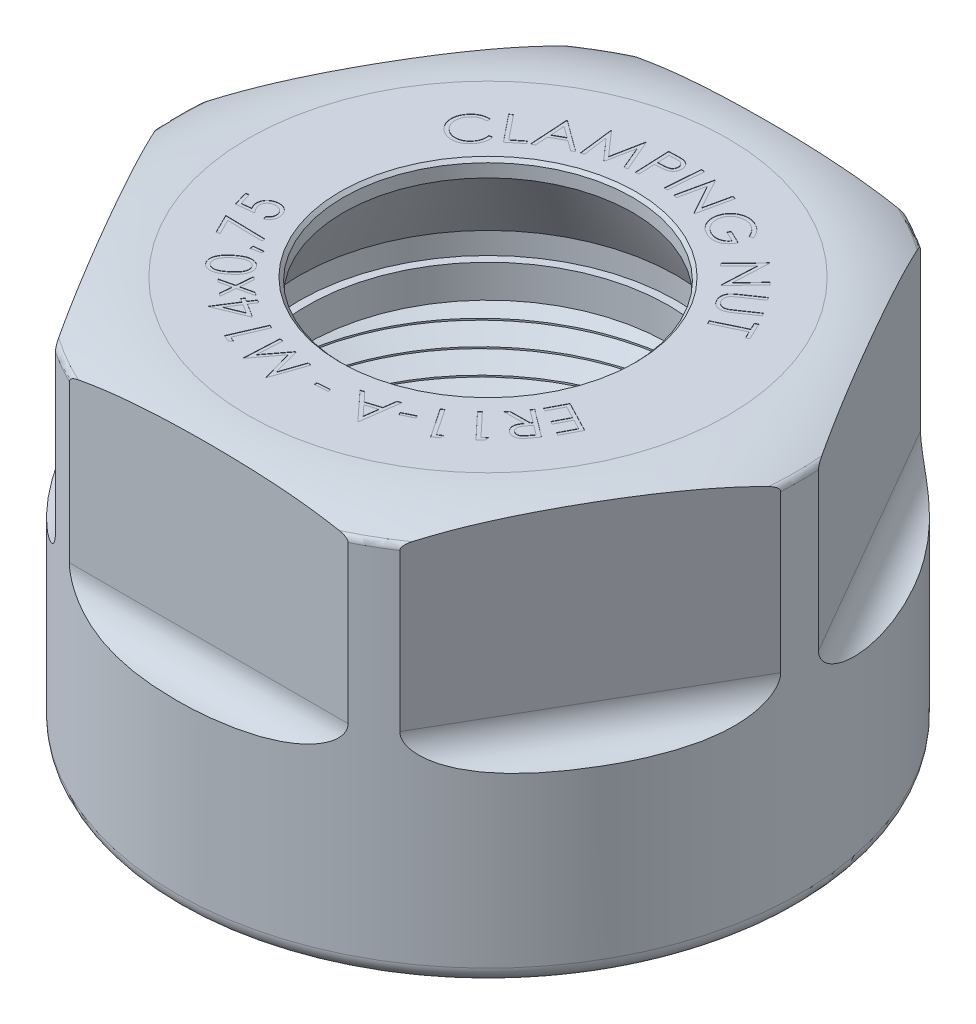
SolidWorks part; units mm, degrees
ref_plane "Front Plane" through (0, 0, 0) normal (0, 0, 1) x (1, 0, 0)
ref_plane "Top Plane" through (0, 0, 0) normal (0, 1, 0) x (1, 0, 0)
ref_plane "Right Plane" through (0, 0, 0) normal (1, 0, 0) x (0, 0, -1)
sketch "Sketch1" plane through (0, 0, 0) normal (0, 1, 0) x (1, 0, 0)
  circle A0 centre (0, 0) radius 9.5
  dimension "D1" = 19
extrude "Boss-Extrude1" add sketch "Sketch1" along normal blind 12
sketch "Sketch2" plane through (0, 12, 0) normal (0, 1, 0) x (1, 0, 0)
  line L1 (9.4825, 0.5758) -> (5.2399, 7.9242)
  line L2 (4.2426, 8.5) -> (-4.2426, 8.5)
  line L3 (-5.2399, 7.9242) -> (-9.4825, 0.5758)
  line L4 (-9.4825, -0.5758) -> (-5.2399, -7.9242)
  line L5 (-4.2426, -8.5) -> (4.2426, -8.5)
  line L6 (5.2399, -7.9242) -> (9.4825, -0.5758)
  circle A0 centre (0, 0) radius 8.5 construction
  circle A1 centre (0, 0) radius 9.5 construction
  arc A2 (-5.2399, 7.9242) -> (-9.4825, 0.5758) centre (0, 0) ccw
  arc A3 (4.2426, 8.5) -> (-4.2426, 8.5) centre (0, 0) ccw
  arc A4 (9.4825, 0.5758) -> (5.2399, 7.9242) centre (0, 0) ccw
  arc A5 (5.2399, -7.9242) -> (9.4825, -0.5758) centre (0, 0) ccw
  arc A6 (-4.2426, -8.5) -> (4.2426, -8.5) centre (0, 0) ccw
  arc A7 (-9.4825, -0.5758) -> (-5.2399, -7.9242) centre (0, 0) ccw
  dimension "D1" = 17
extrude "Cut-Extrude1" cut sketch "Sketch2" against normal blind 6.4
fillet "Fillet1" radius 1 6 edges at (-7.3612, 5.6, 4.25) (-7.3612, 5.6, -4.25) (0, 5.6, -8.5) (7.3612, 5.6, -4.25) (7.3612, 5.6, 4.25) (0, 5.6, 8.5)
sketch "Sketch3" plane through (0, 12, 0) normal (0, 1, 0) x (1, 0, 0)
  circle A0 centre (0, 0) radius 4.4
  dimension "D1" = 8.8
extrude "Cut-Extrude2" cut sketch "Sketch3" against normal up to next
sketch "Sketch5" plane through (0, 0, 0) normal (0, 0, 1) x (1, 0, 0)
  line L0 (-6.4, 0.3464) -> (-6.4, 6.7072)
  line L1 (-9.5, 0) -> (9.5, 0) construction
  line L2 (-6.4, 7.5) -> (-5.5, 7.5)
  line L3 (-5.5, 7.5) -> (-5.5, 8.5)
  line L4 (-5.5, 8.5) -> (-5.75, 8.5)
  line L7 (0, 11.5) -> (0, 0)
  line L8 (0, 0) -> (-6.4, 0)
  line L9 (4.4, 12) -> (-4.4, 12) construction
  line L10 (4.4, 12) -> (-4.4, 12) construction
  line L11 (-4.4, 12) -> (-4.4, 11.5) construction
  line L13 (-4.4, 11.5) -> (-4.4, 10.8242) construction
  line L14 (-4.4, 11.5) -> (0, 11.5)
  line L15 (-5.75, 8.5) -> (-5.75, 9.1617)
  line L16 (-5.75, 9.1617) -> (-4.4, 11.5)
  line L17 (-6.4, 7.5) -> (-7, 7.1536)
  line L18 (-7, 7.1536) -> (-7, 7.0536)
  line L19 (-7, 7.0536) -> (-6.4, 6.7072)
  line L20 (-6.4, 0.3464) -> (-7, 0)
  line L21 (-7, 0) -> (-6.4, 0)
  dimension "D1" = 6.4
  dimension "D2" = 5.5
  dimension "D3" = 1
  dimension "D4" = 30
  dimension "D5" = 0.5
  dimension "D6" = 7.5
  dimension "D7" = 5.75
  dimension "D8" = 60
  dimension "D9" = 7
  dimension "D10" = 0.1
revolve "Cut-Revolve1" cut sketch "Sketch5" angle 360 about L7
sketch "Sketch6" plane through (0, 0, 0) normal (0, 0, 1) x (1, 0, 0)
  line L0 (-9.5, 12) -> (-7.3, 12)
  line L1 (-5.2399, 12) -> (-9.4825, 12) construction
  line L3 (-9.5, 11.5) -> (-9.5, 12)
  line L4 (0, 0) -> (0, 12) construction
  line L5 (4.2426, 12) -> (-4.2426, 12) construction
  arc A0 (-7.3, 12) -> (-9.5, 11.5) centre (-7.3, 6.91) ccw
  dimension "D1" = 2.2
  dimension "D2" = 0.5
revolve "Cut-Revolve2" cut sketch "Sketch6" angle 360 about L4
fillet "Fillet2" radius 0.2 6 edges at (-9.5, 11.5, 0) (-4.75, 11.5, -8.2272) (4.75, 11.5, -8.2272) (9.5, 11.5, 0) (4.75, 11.5, 8.2272) (-4.75, 11.5, 8.2272)
fillet "Fillet3" radius 0.5 1 edges at (0, 0, 9.5)
sketch "Sketch7" plane through (0, 12, 0) normal (0, 1, 0) x (1, 0, 0)
  circle A0 centre (0, 0) radius 5.0417 construction
  text T0 "ER11-A - M14x0,75          CLAMPING NUT" font "Century Gothic" height in points 4
extrude "Cut-Extrude3" cut sketch "Sketch7" against normal blind 0.01
chamfer "Chamfer2" distance 0.1 angle 45 1 edges at (0, 12, 4.4)
sketch "Эскиз1" plane through (0, 0, 0) normal (0, -1, 0) x (1, 0, 0)
  circle A0 centre (0, 0) radius 7
  dimension "D1" = 14
curve "Спираль1" pitch 0.75 height 7.5 turns 10
ref_plane "Плоскость1" through (4.9497, 0, 4.9497) normal (0.707, 0.017, -0.707) x (-0.7068, -0.017, -0.7072)
sketch "Эскиз2" plane through (4.9497, 0, 4.9497) normal (0.707, 0.017, -0.707) x (-0.7068, -0.017, -0.7072)
  line L0 (0.6495, 0) -> (0.075, -0.3317)
  line L1 (0.075, -0.4183) -> (0.6495, -0.75)
  line L2 (0.6495, -0.75) -> (0.6495, 0)
  line L3 (0.075, -0.4183) -> (0, -0.375) construction
  line L4 (0, -0.375) -> (0.075, -0.3317) construction
  arc A0 (0.075, -0.3317) -> (0.075, -0.4183) centre (0.1, -0.375) ccw
  dimension "D3" = 0.05
  dimension "D1" = 60
  dimension "D2" = 0.75
sweep "Вырез-По траектории1" cut profiles "Эскиз2" path "Спираль1"
